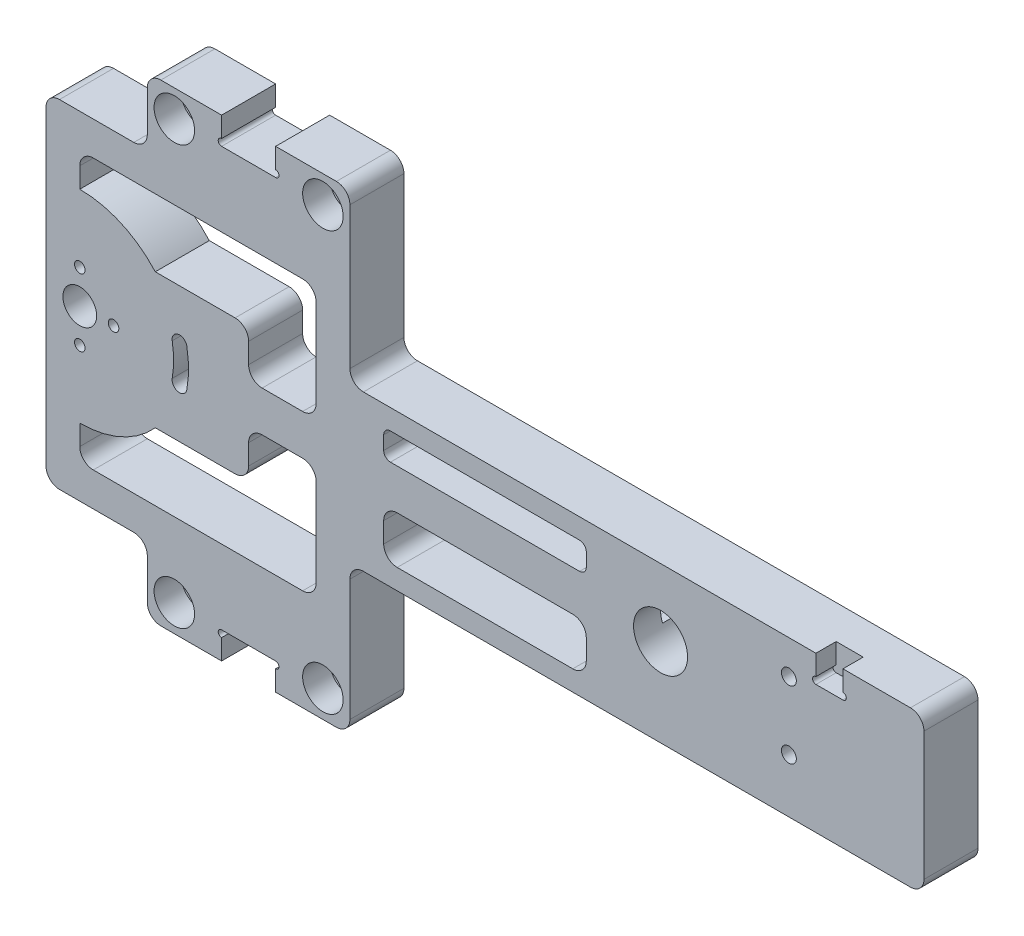
SolidWorks part; units mm, degrees
material "6061 Alloy"
ref_plane "Front Plane" through (0, 0, 0) normal (0, 0, 1) x (1, 0, 0)
ref_plane "Top Plane" through (0, 0, 0) normal (0, 1, 0) x (1, 0, 0)
ref_plane "Right Plane" through (0, 0, 0) normal (1, 0, 0) x (0, 0, -1)
sketch "Sketch1" plane through (0, 0, 0) normal (0, 0, 1) x (1, 0, 0)
  line L0 (-65, 0) -> (65, 0) construction
  line L5 (0, 35) -> (0, -35) construction
  line L6 (-65, 25) -> (-65, -25)
  line L7 (-65, -25) -> (-50, -25)
  line L8 (-50, -25) -> (-50, -35)
  line L9 (-50, -35) -> (-20, -35)
  line L10 (-20, -35) -> (-20, -13)
  line L11 (-20, -13) -> (65, -13)
  line L12 (65, -13) -> (65, 10)
  line L13 (65, 10) -> (-20, 10)
  line L14 (-20, 10) -> (-20, 35)
  line L15 (-20, 35) -> (-50, 35)
  line L16 (-50, 35) -> (-50, 25)
  line L17 (-50, 25) -> (-65, 25)
  dimension "D1" = 70
  dimension "D2" = 130
  dimension "D3" = 15
  dimension "D4" = 10
  dimension "D5" = 10
  dimension "D6" = 13
  dimension "D7" = 30
extrude "Boss-Extrude1" add sketch "Sketch1" along normal blind 8 contours L17 L6 L7 L8 L9 L10 L11 L12 L13 L14 L15 L16
sketch "Sketch3" plane through (0, 0, 8) normal (0, 0, 1) x (1, 0, 0)
  line L1 (-50, -35) -> (-20, -35) construction
  line L2 (-50, -25) -> (-50, -35) construction
  circle A0 centre (-46, -31) radius 3
  circle A2 centre (-24, -31) radius 3
  circle A3 centre (-46, -31) radius 1.6
  circle A5 centre (-24, -31) radius 1.6
  point P7 (0, 0)
  dimension "D1" = 6
  dimension "D2" = 3.2
  dimension "D4" = 4
  dimension "D3" = 22
  dimension "D6" = 4
extrude "Cut-Extrude1" cut sketch "Sketch3" against normal blind 4 contours A0 | A2
extrude "Cut-Extrude2" cut sketch "Sketch3<3>" against normal blind 8 contours A3 | A5
sketch "Sketch3<3>" plane through (0, 0, 8) normal (0, 0, 1) x (1, 0, 0) same geometry as "Sketch3"
sketch "Sketch22" plane through (0, 0, 8) normal (0, 0, 1) x (1, 0, 0)
  line L0 (-50, -35) -> (-20, -35) construction
  line L1 (-39, -31) -> (-31, -31)
  line L2 (-39, -32) -> (-39, -35)
  line L3 (-39, -35) -> (-31, -35)
  line L4 (-31, -32) -> (-31, -35)
  line L5 (-50, -25) -> (-50, -35) construction
  arc A0 (-31, -32) -> (-31, -31) centre (-31, -31.5) ccw
  arc A1 (-39, -31) -> (-39, -32) centre (-39, -31.5) ccw
  point P12 (0, 0)
  dimension "D4" = 1
  dimension "D1" = 8
  dimension "D2" = 11
  dimension "D3" = 4
extrude "Cut-Extrude13" cut sketch "Sketch22" against normal blind 10
mirror "Mirror1" about plane through (0, 0, 0) normal (0, 1, 0) of "Cut-Extrude13", "Cut-Extrude2", "Cut-Extrude1"
sketch "Sketch4" plane through (0, 0, 0) normal (0, 0, -1) x (-1, 0, 0)
  line L0 (65, 25) -> (65, -25) construction
  line L1 (65, 6.245) -> (65, -6.245)
  arc A0 (65, 6.245) -> (65, -6.245) centre (60, 0) ccw
  circle A1 centre (60, 0) radius 2.5
  circle A2 centre (60, 5) radius 0.7835
  circle A3 centre (55, 0) radius 0.7835
  circle A4 centre (60, -5) radius 0.7835
  dimension "D1" = 16
  dimension "D3" = 5
  dimension "D4" = 1.567
  dimension "D5" = 5
  dimension "D6" = 5
  dimension "D7" = 5
  dimension "D2" = 5
extrude "Cut-Extrude3" cut sketch "Sketch4" against normal blind 4
extrude "Cut-Extrude4" cut sketch "Sketch4<2>" against normal blind 8 contours A2 | A3 | A1 | A4
sketch "Sketch4<2>" plane through (0, 0, 0) normal (0, 0, -1) x (-1, 0, 0) same geometry as "Sketch4"
fillet "Fillet1" radius 2 12 edges at (-65, -25, 4) (-50, -25, 4) (-50, -35, 4) (-20, -35, 4) (-20, -13, 4) (65, -13, 4) (65, 10, 4) (-20, 10, 4) (-20, 35, 4) (-50, 35, 4) (-50, 25, 4) (-65, 25, 4)
sketch "Sketch6" plane through (0, 0, 0) normal (0, 0, -1) x (-1, 0, 0)
  line L0 (-65, -11) -> (-65, 8) construction
  line L1 (-63, 10) -> (18, 10) construction
  circle A0 centre (-45, 5) radius 1.1
  circle A1 centre (-45, 5) radius 2
  circle A2 centre (-45, -5) radius 1.1
  circle A3 centre (-45, -5) radius 2
  dimension "D1" = 4
  dimension "D2" = 2.2
  dimension "D3" = 20
  dimension "D4" = 5
  dimension "D5" = 10
extrude "Cut-Extrude6" cut sketch "Sketch6" against normal blind 4 contours A1 | A3
extrude "Cut-Extrude7" cut sketch "Sketch6<3>" against normal blind 8 contours A0 | A2
sketch "Sketch6<3>" plane through (0, 0, 0) normal (0, 0, -1) x (-1, 0, 0) same geometry as "Sketch6"
sketch "Sketch7" plane through (0, 0, 0) normal (0, 0, -1) x (-1, 0, 0)
  line L0 (-65, -11) -> (-65, 8) construction
  line L1 (-31, 0) -> (-21, 0) construction
  line L2 (-31, 1.5) -> (-21, 1.5)
  line L3 (-31, -1.5) -> (-21, -1.5)
  circle A0 centre (-26, 0) radius 4
  arc A1 (-31, 1.5) -> (-31, -1.5) centre (-31, 0) ccw
  arc A2 (-21, -1.5) -> (-21, 1.5) centre (-21, 0) ccw
  point P7 (-26, 0)
  dimension "D2" = 8
  dimension "D3" = 1.5
  dimension "D1" = 39
  dimension "D4" = 5
extrude "Cut-Extrude8" cut sketch "Sketch7" against normal blind 8 contours A0
extrude "Cut-Extrude9" cut sketch "Sketch7<3>" against normal blind 4 contours L2 A2 L3 A1
sketch "Sketch7<3>" plane through (0, 0, 0) normal (0, 0, -1) x (-1, 0, 0) same geometry as "Sketch7"
sketch "Sketch9" plane through (0, 0, 0) normal (0, 0, -1) x (-1, 0, 0)
  line L0 (-15, 0) -> (65, 0) construction
  line L1 (65, -6.245) -> (65, 6.245) construction
  line L2 (35, 10) -> (35, 3)
  line L3 (65, 23) -> (65, 6.245) construction
  line L5 (-63, 10) -> (18, 10) construction
  line L6 (35, 10) -> (48.8197, 10)
  line L7 (35, -10) -> (48.8197, -10)
  line L8 (60, 15) -> (60, 20)
  line L9 (60, 20) -> (25, 20)
  line L10 (25, 20) -> (25, 3)
  line L11 (52, 25) -> (63, 25) construction
  line L12 (20, 12) -> (20, 33) construction
  line L13 (25, 3) -> (35, 3)
  line L14 (25, -3) -> (35, -3)
  line L15 (60, -15) -> (60, -20)
  line L16 (60, -20) -> (25, -20)
  line L17 (35, -3) -> (35, -10)
  line L18 (25, -3) -> (25, -20)
  line L19 (-15, 7) -> (15, 7)
  line L20 (-15, 7) -> (-15, 3)
  line L21 (-15, 3) -> (15, 3)
  line L22 (15, 7) -> (15, 3)
  line L23 (-15, -10) -> (15, -10)
  line L24 (-15, -10) -> (-15, -3)
  line L25 (-15, -3) -> (15, -3)
  line L26 (15, -10) -> (15, -3)
  line L27 (18, -13) -> (-63, -13) construction
  arc A0 (60, 15) -> (48.8197, 10) centre (60, 0) ccw
  arc A1 (48.8197, -10) -> (60, -15) centre (60, 0) ccw
  point P30 (20, 0)
  dimension "D3" = 30
  dimension "D1" = 30
  dimension "D2" = 20
  dimension "D4" = 15
  dimension "D5" = 5
  dimension "D6" = 5
  dimension "D7" = 3
  dimension "D8" = 10
  dimension "D9" = 10
  dimension "D10" = 10
  dimension "D11" = 0
  dimension "D12" = 0
  dimension "D13" = 3
  dimension "D14" = 3
  dimension "D15" = 3
  dimension "D16" = 3
extrude "Cut-Extrude10" cut sketch "Sketch9" against normal blind 8
fillet "Fillet2" radius 2 14 edges at (-25, -20, 4) (-35, -10, 4) (-35, -3, 4) (-25, -3, 4) (-35, 10, 4) (-35, 3, 4) (-25, 3, 4) (-60, 20, 4) (-25, 20, 4) (-15, -10, 4) (15, -10, 4) (-15, -3, 4) (15, -3, 4) (-60, -20, 4)
fillet "Fillet3" radius 1 4 edges at (-15, 3, 4) (-15, 7, 4) (15, 7, 4) (15, 3, 4)
hole_wizard "Ø3.0mm Dowel Hole1" positions "Sketch10" profile "Sketch11" hole size "Ø3.0" standard "ANSI Metric"
sketch "Sketch10" plane through (0, -13, 0) normal (0, -1, 0) x (-1, 0, 0)
  line L1 (-65, -8) -> (-65, 0) construction
  line L2 (18, -8) -> (-63, -8) construction
  point P3 (-38, -4)
  point P9 (-53, -4)
  dimension "D1" = 4
  dimension "D2" = 12
  dimension "D3" = 15
sketch "Sketch11" plane through (38, -13, 4) normal (1, 0, 0) x (0, 0, -1)
  line L0 (0, 0) -> (0, 7)
  line L1 (0, 7) -> (1.5, 6.0987)
  line L2 (1.5, 6.0987) -> (1.5, 0)
  line L5 (1.5, 0) -> (0, 0)
  line L10 (0, 7) -> (-1.5, 6.0987) construction
  line L11 (0, -6.35) -> (0, 107.95) construction
  dimension "Hole Dia." = 3
  dimension "Hole Depth" = 7
  dimension "Drill Angle" = 118
hole_wizard "Ø2.5mm Dowel Hole1" positions "Sketch16" profile "Sketch17" hole size "Ø2.5" standard "ANSI Metric"
sketch "Sketch16" plane through (0, -13, 0) normal (0, -1, 0) x (-1, 0, 0)
  line L1 (18, -8) -> (-63, -8) construction
  point P0 (-48, -4)
  point P2 (-43, -4)
  dimension "D1" = 5
  dimension "D2" = 5
  dimension "D3" = 4
sketch "Sketch17" plane through (48, -13, 4) normal (1, 0, 0) x (0, 0, -1)
  line L0 (0, 0) -> (0, 4.7511)
  line L1 (0, 4.7511) -> (1.25, 4)
  line L2 (1.25, 4) -> (1.25, 0)
  line L5 (1.25, 0) -> (0, 0)
  line L10 (0, 4.7511) -> (-1.25, 4) construction
  line L11 (0, -6.35) -> (0, 107.95) construction
  dimension "Hole Dia." = 2.5
  dimension "Hole Depth" = 4
  dimension "Drill Angle" = 118
sketch "Sketch21" plane through (0, 0, 0) normal (0, 0, -1) x (-1, 0, 0)
  line L0 (0, 0) -> (60, 0) construction
  arc A0 (45.2279, 2.6047) -> (45.2279, -2.6047) centre (60, 0) ccw construction
  arc A1 (43.2583, 2.952) -> (43.2583, -2.952) centre (60, 0) ccw
  arc A2 (47.1975, 2.2574) -> (47.1975, -2.2574) centre (60, 0) ccw
  arc A3 (47.1975, 2.2574) -> (43.2583, 2.952) centre (45.2279, 2.6047) ccw
  arc A4 (43.2583, -2.952) -> (47.1975, -2.2574) centre (45.2279, -2.6047) ccw
  arc A5 (45.2279, 2.6047) -> (45.2279, -2.6047) centre (60, 0) ccw construction
  arc A6 (44.1446, 2.7957) -> (44.1446, -2.7957) centre (60, 0) ccw
  arc A7 (46.3112, 2.4137) -> (46.3112, -2.4137) centre (60, 0) ccw
  arc A8 (46.3112, 2.4137) -> (44.1446, 2.7957) centre (45.2279, 2.6047) ccw
  arc A9 (44.1446, -2.7957) -> (46.3112, -2.4137) centre (45.2279, -2.6047) ccw
  point P4 (45, 0)
  point P9 (45, 0)
  dimension "D2" = 2
  dimension "D4" = 1.1
  dimension "D1" = 20
  dimension "D3" = 15
extrude "Cut-Extrude11" cut sketch "Sketch21" against normal blind 4 contours A3 A1 A4 A2
extrude "Cut-Extrude12" cut sketch "Sketch21<3>" against normal blind 8 contours A8 A6 A9 A7
sketch "Sketch21<3>" plane through (0, 0, 0) normal (0, 0, -1) x (-1, 0, 0) same geometry as "Sketch21"
sketch "Sketch23" plane through (0, 0, 8) normal (0, 0, 1) x (1, 0, 0)
  line L0 (63, 10) -> (-18, 10) construction
  line L1 (49, 10) -> (53, 10)
  line L2 (49, 10) -> (49, 7)
  line L3 (49, 6) -> (53, 6)
  line L4 (53, 10) -> (53, 7)
  circle A0 centre (45, 5) radius 1.1 construction
  arc A1 (49, 7) -> (49, 6) centre (49, 6.5) ccw
  arc A2 (53, 6) -> (53, 7) centre (53, 6.5) ccw
  point P12 (0, 0)
  dimension "D1" = 4
  dimension "D4" = 1
  dimension "D2" = 4
  dimension "D3" = 4
extrude "Cut-Extrude14" cut sketch "Sketch23" against normal blind 3
